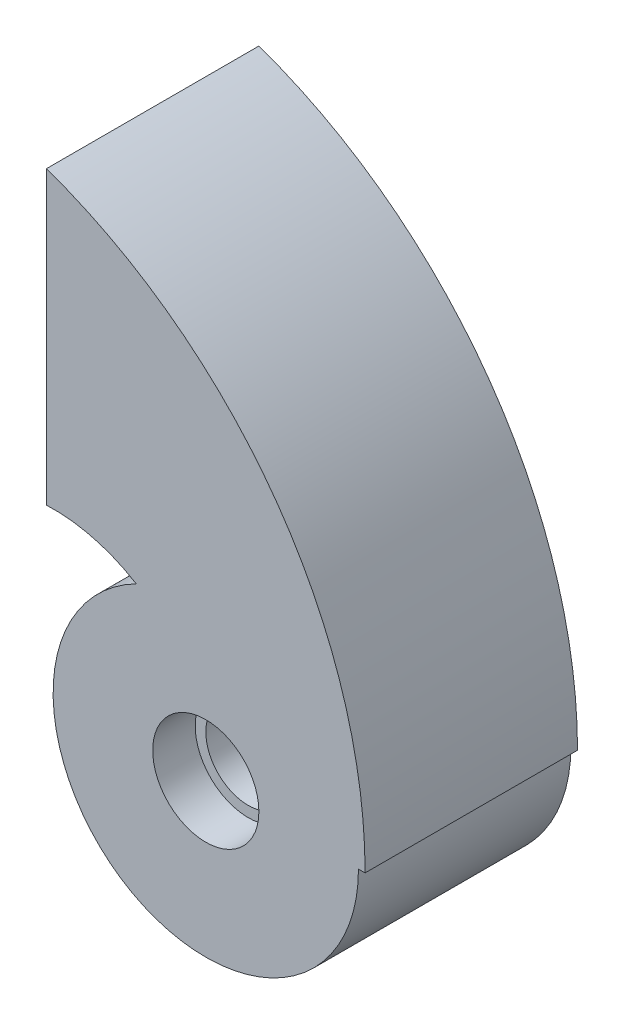
SolidWorks part; units mm, degrees
ref_plane "前视基准面" through (0, 0, 0) normal (0, 0, 1) x (1, 0, 0)
ref_plane "上视基准面" through (0, 0, 0) normal (0, 1, 0) x (1, 0, 0)
ref_plane "右视基准面" through (0, 0, 0) normal (1, 0, 0) x (0, 0, -1)
sketch "草图1" plane through (0, 0, 0) normal (0, 0, 1) x (1, 0, 0)
  circle A0 centre (0, 0) radius 14.375
  circle A1 centre (0, 0) radius 15 construction
  dimension "D1" = 28.75
  dimension "D2" = 30
extrude "凸台-拉伸1" add sketch "草图1" along normal blind 10 and the other way blind 10
sketch "草图2" plane through (0, 0, 10) normal (0, 0, 1) x (1, 0, 0)
  line L0 (0, 0) -> (-30, 0) construction
  line L1 (-15, 42.4264) -> (0, 0) construction
  line L2 (-15, 42.4264) -> (-15, 14.987)
  line L3 (0.625, 0) -> (15, 0)
  circle A0 centre (0, 0) radius 14.375 construction
  arc A1 (15, 0) -> (-15, 42.4264) centre (-30, 0) ccw
  circle A2 centre (-14.375, 0) radius 30 construction
  arc A3 (-15, 14.987) -> (0.625, 0) centre (-14.375, 0) cw
  circle A5 centre (0, 0) radius 15 construction
  dimension "D2" = 45
  dimension "D3" = 60
  dimension "D4" = 15
extrude "凸台-拉伸2" add sketch "草图2" against normal up to surface (20 mm away) up to face at (14.375, 0, -10)
sketch "草图10" plane through (0, 0, 10) normal (0, 0, 1) x (1, 0, 0)
  circle A0 centre (0, 0) radius 4
  dimension "D1" = 8
extrude "切除-拉伸1" cut sketch "草图10" against normal through all
sketch "草图11" plane through (0, 0, -10) normal (0, 0, -1) x (-1, 0, 0)
  circle A0 centre (0, 0) radius 5
  dimension "D1" = 10
extrude "切除-拉伸2" cut sketch "草图11" against normal blind 4
sketch "草图12" plane through (0, 0, 10) normal (0, 0, 1) x (1, 0, 0)
  circle A0 centre (0, 0) radius 5
  dimension "D1" = 10
extrude "切除-拉伸3" cut sketch "草图12" against normal blind 4
